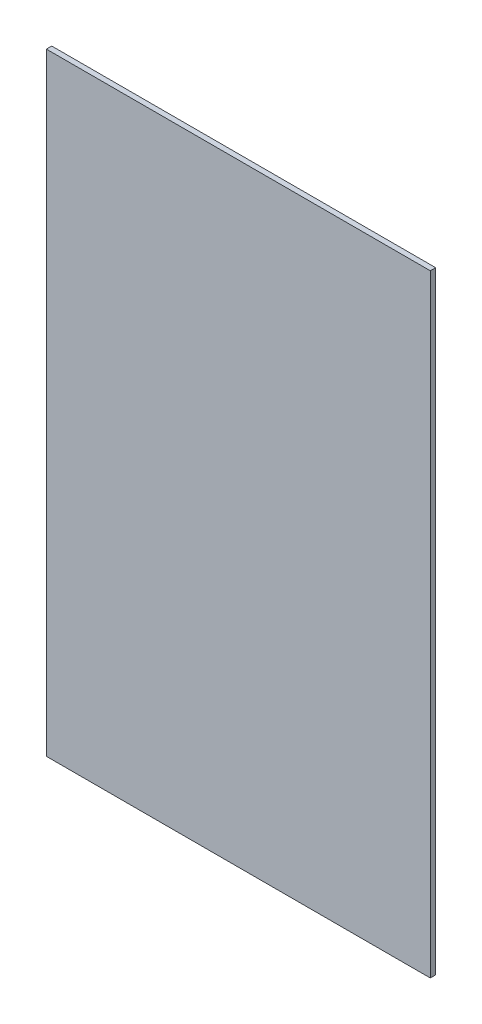
SolidWorks part; units mm, degrees
ref_plane "Front Plane" through (0, 0, 0) normal (0, 0, 1) x (1, 0, 0)
ref_plane "Top Plane" through (0, 0, 0) normal (0, 1, 0) x (1, 0, 0)
ref_plane "Right Plane" through (0, 0, 0) normal (1, 0, 0) x (0, 0, -1)
sketch "Sketch1" plane through (0, 0, -122.5) normal (0, 0, -1) x (-1, 0, 0)
  line L0 (107.5, 330) -> (-107.5, 330) construction
  line L1 (-107.5, 330) -> (107.5, 330)
  line L2 (-107.5, 330) -> (-107.5, -13)
  line L3 (-107.5, -13) -> (107.5, -13)
  line L4 (107.5, 330) -> (107.5, -13)
  line L5 (-107.5, 10) -> (-107.5, 310) construction
  line L6 (107.5, 10) -> (107.5, 310) construction
  line L9 (107.5, -13) -> (-107.5, -13) construction
  point P12 (107.5, -10)
  point P13 (0, 0)
  point P14 (0, 0)
  point P15 (0, 0)
  point P16 (0, 0)
  point P17 (0, 0)
base flange "Base-Flange1" sketch "Sketch1" thickness 3 reverse thickness direction yes parameters "D1"=3
sketch "Bend-Lines1" [suppressed] plane through (0, 0, 0) normal (0, 1, 0) x (1, 0, 0)
sketch "Bounding-Box1" [suppressed] plane through (0, 0, 0) normal (0, 1, 0) x (1, 0, 0)
sheet metal parameters "Sheet-Metal1" thickness 3 parameters "D1"=3
flat pattern "Flat-Pattern1" [suppressed]
sketch "Bend-Lines2" plane through (0, 0, 0) normal (0, 1, 0) x (1, 0, 0)
sketch3d "Bounding-Box2" [suppressed]
  line L0 (107.5, 330, 0) -> (107.5, -13, 0) construction
  line L1 (-107.5, 330, 0) -> (-107.5, -13, 0) construction
  line L2 (107.5, 330, 0) -> (-107.5, 330, 0) construction
  line L3 (107.5, -13, 0) -> (-107.5, -13, 0) construction
